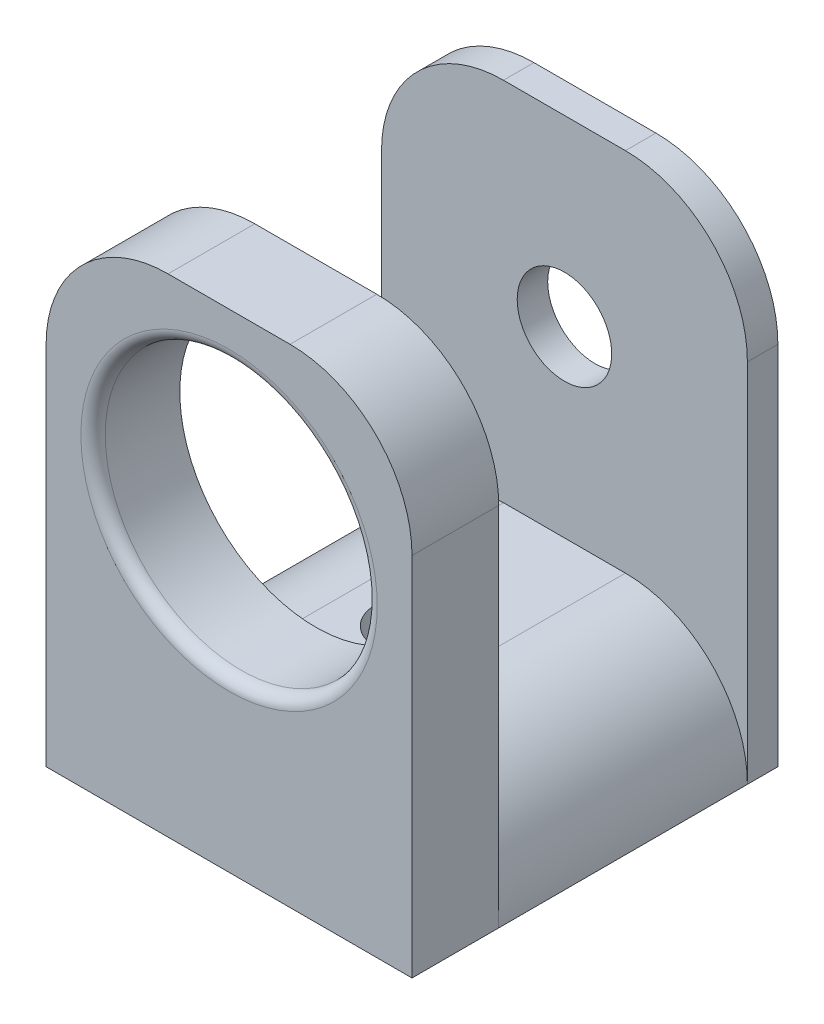
SolidWorks part; units mm, degrees
ref_plane "Front Plane" through (0, 0, 0) normal (0, 0, 1) x (1, 0, 0)
ref_plane "Top Plane" through (0, 0, 0) normal (0, 1, 0) x (1, 0, 0)
ref_plane "Right Plane" through (0, 0, 0) normal (1, 0, 0) x (0, 0, -1)
sketch "Sketch1" plane through (0, 0, 0) normal (0, 1, 0) x (1, 0, 0)
  line L1 (18.1877, 2.1165) -> (-11.8123, 2.1165)
  line L2 (18.1877, 2.1165) -> (18.1877, 32.1165)
  line L3 (18.1877, 32.1165) -> (-11.8123, 32.1165)
  line L4 (-11.8123, 2.1165) -> (-11.8123, 32.1165)
  dimension "D1" = 30
  dimension "D2" = 30
extrude "Boss-Extrude1" add sketch "Sketch1" along normal blind 10
sketch "Sketch2" plane through (0, 10, 0) normal (0, 1, 0) x (1, 0, 0)
  line L0 (18.1877, 2.1165) -> (18.1877, 32.1165) construction
  line L1 (-11.8123, 32.1165) -> (18.1877, 32.1165)
  line L2 (-11.8123, 32.1165) -> (-11.8123, 29.6165)
  line L3 (-11.8123, 29.6165) -> (18.1877, 29.6165)
  line L4 (18.1877, 32.1165) -> (18.1877, 29.6165)
  dimension "D1" = 2.5
extrude "Boss-Extrude2" add sketch "Sketch2" along normal blind 30
sketch "Sketch3" plane through (0, 10, 0) normal (0, 1, 0) x (1, 0, 0)
  line L0 (18.1877, 2.1165) -> (18.1877, 29.6165) construction
  line L1 (-11.8123, 2.1165) -> (18.1877, 2.1165)
  line L2 (-11.8123, 2.1165) -> (-11.8123, 9.2285)
  line L3 (-11.8123, 9.2285) -> (18.1877, 9.2285)
  line L4 (18.1877, 2.1165) -> (18.1877, 9.2285)
  dimension "D1" = 7.112
extrude "Boss-Extrude3" add sketch "Sketch3" along normal blind 30
sketch "Sketch4" plane through (0, 0, -2.1165) normal (0, 0, 1) x (1, 0, 0)
  line L0 (18.1877, 40) -> (18.1877, 0) construction
  line L1 (-11.8123, 40) -> (18.1877, 40) construction
  circle A0 centre (3.1877, 25) radius 11.1506
  dimension "D1" = 15
  dimension "D2" = 15
extrude "Cut-Extrude2" cut sketch "Sketch4" against normal up to next
fillet "Fillet2" radius 1 1 edges at (14.3383, 25, -2.1165)
sketch "Sketch5" plane through (0, 0, -32.1165) normal (0, 0, -1) x (-1, 0, 0)
  line L0 (-18.1877, 40) -> (11.8123, 40) construction
  line L1 (-18.1877, 40) -> (-18.1877, 0) construction
  circle A0 centre (-3.1877, 25) radius 3.875
  dimension "D1" = 15
  dimension "D2" = 15
extrude "Cut-Extrude3" cut sketch "Sketch5" against normal blind 30
sketch "Sketch6" plane through (0, 0, 0) normal (0, -1, 0) x (-1, 0, 0)
  line L0 (-18.1877, 2.1165) -> (-18.1877, 32.1165) construction
  line L1 (11.8123, 2.1165) -> (-18.1877, 2.1165) construction
  circle A0 centre (-3.1877, 17.1165) radius 3
  dimension "D1" = 15
  dimension "D2" = 15
extrude "Cut-Extrude4" cut sketch "Sketch6" against normal blind 30
fillet "Fillet3" radius 1 1 edges at (3.1877, 0, -20.1165)
fillet "Fillet4" radius 10 2 edges at (-11.8123, 40, -30.8665) (18.1877, 40, -30.8665)
fillet "Fillet5" radius 10 1 edges
fillet "Fillet6" radius 10 1 edges
fillet "Fillet7" radius 10 2 edges at (18.1877, 40, -5.6725) (-11.8123, 40, -5.6725)
